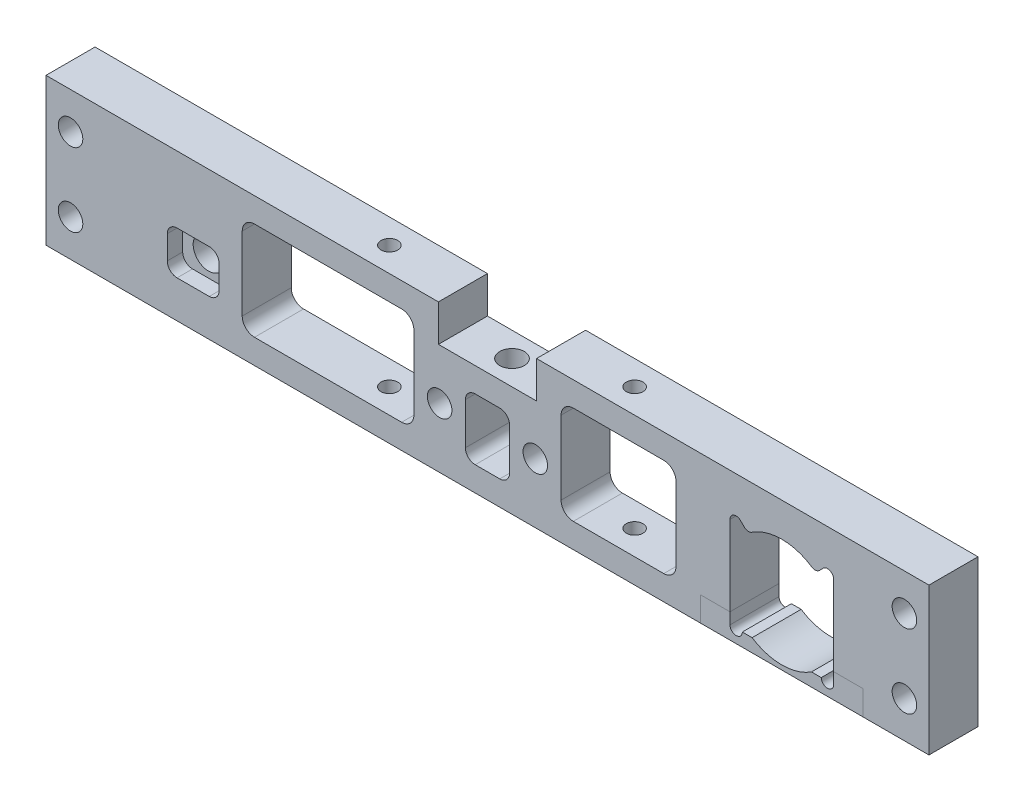
SolidWorks part; units mm, degrees
material "6061-T6 (SS)"
ref_plane "Front Plane" through (0, 0, 0) normal (0, 0, 1) x (1, 0, 0)
ref_plane "Top Plane" through (0, 0, 0) normal (0, 1, 0) x (1, 0, 0)
ref_plane "Right Plane" through (0, 0, 0) normal (1, 0, 0) x (0, 0, -1)
sketch "Sketch1" plane through (0, 0, 0) normal (0, 0, 1) x (1, 0, 0)
  line L1 (-190.5, -19.05) -> (38.1, -19.05)
  line L2 (-190.5, -19.05) -> (-190.5, 19.05)
  line L3 (-190.5, 19.05) -> (38.1, 19.05)
  line L4 (38.1, -19.05) -> (38.1, 19.05)
  line L5 (-190.5, -19.05) -> (38.1, 19.05) construction
  line L6 (-190.5, 19.05) -> (38.1, -19.05) construction
  line L7 (-190.5, 19.05) -> (38.1, 19.05)
  line L8 (-190.5, 19.05) -> (-190.5, -19.05)
  line L11 (-190.5, -19.05) -> (38.1, -19.05)
  line L12 (-190.5, -19.05) -> (-190.5, 19.05)
  line L15 (38.1, -19.05) -> (-190.5, -19.05)
  line L16 (38.1, -19.05) -> (38.1, 19.05)
  line L20 (38.1, -19.05) -> (38.1, 19.05)
  point P0 (0, 0)
  point P14 (-76.2, 0)
  dimension "D1" = 38.1
  dimension "D2" = 228.6
  dimension "D3" = 38.1
extrude "Boss-Extrude1" add sketch "Sketch1" along normal blind 12.7
sketch "Sketch5" plane through (0, 0, 12.7) normal (0, 0, 1) x (1, 0, 0)
  line L0 (0, -3.81) -> (11.8187, 8.0087) construction
  line L1 (0, -3.81) -> (11.8187, -3.81) construction
  line L2 (0, -3.81) -> (0, 8.0087) construction
  line L3 (0, 8.0087) -> (11.8187, 8.0087) construction
  line L4 (11.8187, -3.81) -> (11.8187, 8.0087) construction
  line L5 (-10.6872, 9.1402) -> (-8.7721, 7.2252)
  line L6 (0, -3.81) -> (11.8187, -3.81) construction
  line L7 (0, -3.81) -> (0, -15.6287) construction
  line L8 (0, -15.6287) -> (11.8187, -15.6287) construction
  line L9 (11.8187, -3.81) -> (11.8187, -15.6287) construction
  line L10 (0, -3.81) -> (-11.8187, -3.81) construction
  line L11 (0, -3.81) -> (0, -15.6287) construction
  line L12 (0, -15.6287) -> (-11.8187, -15.6287) construction
  line L13 (-11.8187, -3.81) -> (-11.8187, -15.6287) construction
  line L14 (0, -3.81) -> (-11.8187, -3.81) construction
  line L15 (0, -3.81) -> (0, 8.0087) construction
  line L16 (0, 8.0087) -> (-11.8187, 8.0087) construction
  line L17 (-11.8187, -3.81) -> (-11.8187, 8.0087) construction
  line L18 (-13.4189, 8.0087) -> (-13.4189, -15.6287)
  line L19 (13.4189, 8.0087) -> (13.4189, -15.6287)
  line L20 (10.9269, 9.3374) -> (8.7958, 7.2063)
  line L21 (-13.4189, -15.6287) -> (-13.4189, -19.05)
  line L22 (-190.5, -19.05) -> (38.1, -19.05) construction
  line L23 (-13.4189, -19.05) -> (13.4189, -19.05)
  line L24 (13.4189, -19.05) -> (13.4189, -15.6287)
  line L25 (-10.2185, -15.6287) -> (-7.6839, -15.6287)
  line L26 (10.2185, -15.6287) -> (7.6839, -15.6287)
  circle A0 centre (0, -3.81) radius 14.097 construction
  circle A1 centre (11.8187, 8.0087) radius 1.6002
  circle A2 centre (-11.8187, 8.0087) radius 1.6002
  circle A3 centre (-11.8187, -15.6287) radius 1.6002
  circle A4 centre (11.8187, -15.6287) radius 1.6002
  arc A5 (-8.7721, 7.2252) -> (8.7958, 7.2063) centre (0, -3.81) cw
  arc A6 (-7.6839, -15.6287) -> (7.6839, -15.6287) centre (0, -3.81) ccw
  point P6 (9.9681, 6.1581)
  point P7 (10.6872, 6.8772)
  line M8 (-190.5, -19.05) -> (38.1, -19.05)
  dimension "D1" = 28.194
  dimension "D2" = 3.2004
  dimension "D3" = 1.017
  dimension "D4" = 45
  dimension "D5" = 45
  dimension "D6" = 15.24
extrude "Cut-Extrude4" cut sketch "Sketch5" against normal through all contours A5 L5 A2 L18 A3 L21 L24 A4 L19 A1 L20 M8 | A4 | A3 | A2 | A1 L20
fillet "Fillet1" radius 1.5875 2 edges at (8.7958, 7.2063, 6.35) (-8.7721, 7.2252, 6.35)
sketch "Sketch6" plane through (0, 0, 12.7) normal (0, 0, 1) x (1, 0, 0)
  line L0 (-190.5, 19.05) -> (38.1, 19.05) construction
  line L1 (-88.9, 19.05) -> (-63.5, 19.05)
  line L2 (-88.9, 19.05) -> (-88.9, 9.525)
  line L3 (-88.9, 9.525) -> (-63.5, 9.525)
  line L4 (-63.5, 19.05) -> (-63.5, 9.525)
  point P6 (-76.2, 9.525)
  point P7 (-76.2, 19.05)
  point P8 (-88.9, 19.05)
  dimension "D1" = 9.525
  dimension "D2" = 25.4
  dimension "D3" = 0
extrude "Cut-Extrude5" cut sketch "Sketch6" against normal through all
sketch "Sketch7" plane through (0, 0, 12.7) normal (0, 0, 1) x (1, 0, 0)
  line L0 (-88.9, 9.525) -> (-63.5, 9.525) construction
  line L1 (-81.915, -12.7) -> (-70.485, -12.7)
  line L2 (-81.915, -12.7) -> (-81.915, 3.175)
  line L3 (-81.915, 3.175) -> (-70.485, 3.175)
  line L4 (-70.485, -12.7) -> (-70.485, 3.175)
  line L5 (-190.5, -19.05) -> (38.1, -19.05) construction
  point P4 (-76.2, 9.525)
  point P5 (-76.2, 3.175)
  dimension "D1" = 11.43
  dimension "D2" = 6.35
  dimension "D3" = 6.35
extrude "Cut-Extrude6" cut sketch "Sketch7" against normal through all
sketch "Sketch8" plane through (0, 9.525, 0) normal (0, 1, 0) x (1, 0, 0)
  line L0 (-88.9, 0) -> (-63.5, 0) construction
  line L1 (-88.9, -12.7) -> (-63.5, -12.7) construction
  circle A0 centre (-76.2, -6.35) radius 3.175
  point P2 (-76.2, 0)
  point P3 (-76.2, -12.7)
  dimension "D1" = 6.35
  dimension "D2" = 6.35
extrude "Cut-Extrude7" cut sketch "Sketch8" against normal up to surface (6.35 mm away) up to face at (-76.2, 3.175, 6.35)
sketch "Sketch9" plane through (0, 0, 0) normal (0, 0, -1) x (-1, 0, 0)
  line L0 (-38.1, -19.05) -> (-38.1, 19.05) construction
  line L1 (-31.75, 9.525) -> (184.15, 9.525) construction
  line L2 (-31.75, 9.525) -> (-31.75, -9.525) construction
  line L3 (-31.75, -9.525) -> (184.15, -9.525) construction
  line L4 (184.15, 9.525) -> (184.15, -9.525) construction
  line L5 (190.5, -19.05) -> (190.5, 19.05) construction
  line L6 (190.5, 19.05) -> (88.9, 19.05) construction
  line L7 (190.5, -19.05) -> (-38.1, -19.05) construction
  circle A0 centre (-31.75, 9.525) radius 3.175
  circle A1 centre (-31.75, -9.525) radius 3.175
  circle A2 centre (184.15, 9.525) radius 3.175
  circle A3 centre (184.15, -9.525) radius 3.175
  dimension "D2" = 6.35
  dimension "D3" = 6.35
  dimension "D1" = 6.35
  dimension "D4" = 9.525
  dimension "D5" = 9.525
extrude "Cut-Extrude8" cut sketch "Sketch9" against normal through all
sketch "Sketch10" plane through (0, 0, 0) normal (0, 0, -1) x (-1, 0, 0)
  circle A0 centre (-31.75, 9.525) radius 4.7625
  circle A1 centre (-31.75, -9.525) radius 4.7625
  circle A2 centre (184.15, 9.525) radius 4.7625
  circle A3 centre (184.15, -9.525) radius 4.7625
  dimension "D1" = 9.525
extrude "Cut-Extrude9" cut sketch "Sketch10" against normal blind 6.35
sketch "Sketch11" plane through (0, 0, 0) normal (0, 0, -1) x (-1, 0, 0)
  line L0 (-21.0389, -19.05) -> (-21.0389, -12.7)
  line L1 (190.5, -19.05) -> (-38.1, -19.05) construction
  line L2 (-21.0389, -12.7) -> (21.0389, -12.7)
  line L3 (21.0389, -12.7) -> (21.0389, -19.05)
  line L4 (-13.4189, 8.0087) -> (-13.4189, -15.6287) construction
  line L5 (13.4189, 8.0087) -> (13.4189, -15.6287) construction
  dimension "D1" = 7.62
  dimension "D2" = 7.62
  dimension "D3" = 6.35
surface "Surface-Extrude1" sketch "Sketch11" parameters "D1"=12.7
split "Split1" trimming surface bodies 113 bodies to split 112 resulting bodies 114 115
fillet "Fillet2" radius 2.54 4 edges at (-70.485, -12.7, 6.35) (-81.915, 3.175, 6.35) (-70.485, 3.175, 6.35) (-81.915, -12.7, 6.35)
sketch "Sketch12" plane through (0, -19.05, 0) normal (0, -1, 0) x (1, 0, 0)
  line L0 (-21.0389, 12.7) -> (21.0389, 12.7) construction
  line L1 (-21.0389, 0) -> (-21.0389, 12.7) construction
  line L2 (21.0389, 12.7) -> (21.0389, 0) construction
  circle A0 centre (-17.2289, 6.35) radius 1.4224
  circle A1 centre (17.2289, 6.35) radius 1.4224
  dimension "D3" = 2.8448
  dimension "D4" = 2.8448
  dimension "D1" = 6.35
  dimension "D2" = 6.35
  dimension "D5" = 3.81
  dimension "D6" = 3.81
extrude "Cut-Extrude10" cut sketch "Sketch12" against normal blind 15.24
chamfer "Chamfer1" distance 2.1082 angle 41 1 edges at (18.6513, -19.05, 6.35) first distance on face at (17.2289, -12.7, 7.7724)
chamfer "Chamfer2" distance 2.1082 angle 41 1 edges at (-15.8065, -19.05, 6.35) first distance on face at (-17.2289, -12.7, 7.7724)
sketch "Sketch13" plane through (0, 0, 0) normal (0, 0, -1) x (-1, 0, 0)
  line L0 (63.5, 19.05) -> (-38.1, 19.05) construction
  line L1 (57.15, 12.7) -> (27.3889, 12.7)
  line L2 (57.15, 12.7) -> (57.15, -12.7)
  line L3 (57.15, -12.7) -> (27.3889, -12.7)
  line L4 (27.3889, 12.7) -> (27.3889, -12.7)
  line L5 (190.5, -19.05) -> (21.0389, -19.05) construction
  line L6 (21.0389, -12.7) -> (21.0389, -19.05) construction
  line L7 (63.5, 9.525) -> (63.5, 19.05) construction
  line L8 (88.9, 19.05) -> (88.9, 9.525) construction
  line L9 (95.25, 12.7) -> (139.7, 12.7)
  line L10 (95.25, 12.7) -> (95.25, -12.7)
  line L11 (95.25, -12.7) -> (139.7, -12.7)
  line L12 (139.7, 12.7) -> (139.7, -12.7)
  line L13 (190.5, 19.05) -> (88.9, 19.05) construction
  point P12 (63.5, 14.2875)
  dimension "D1" = 6.35
  dimension "D2" = 6.35
  dimension "D3" = 6.35
  dimension "D4" = 6.35
  dimension "D5" = 6.35
  dimension "D6" = 6.35
  dimension "D7" = 6.35
  dimension "D8" = 44.45
extrude "Cut-Extrude11" cut sketch "Sketch13" against normal through all
fillet "Fillet3" radius 3.175 8 edges at (-57.15, -12.7, 6.35) (-57.15, 12.7, 6.35) (-27.3889, 12.7, 6.35) (-27.3889, -12.7, 6.35) (-95.25, 12.7, 6.35) (-139.7, 12.7, 6.35) (-139.7, -12.7, 6.35) (-95.25, -12.7, 6.35)
sketch "Sketch14" plane through (0, 19.05, 0) normal (0, 1, 0) x (1, 0, 0)
  line L0 (-190.5, 0) -> (-88.9, 0) construction
  line L1 (-63.5, 0) -> (38.1, 0) construction
  line L2 (-63.5, 0) -> (-63.5, -12.7) construction
  line L3 (-88.9, 0) -> (-88.9, -12.7) construction
  circle A0 centre (-107.95, -6.35) radius 2.159
  circle A1 centre (-44.45, -6.35) radius 2.159
  dimension "D1" = 4.318
  dimension "D2" = 4.318
  dimension "D3" = 6.35
  dimension "D4" = 6.35
  dimension "D5" = 19.05
  dimension "D6" = 19.05
extrude "Cut-Extrude12" cut sketch "Sketch14" against normal through all
sketch "Sketch15" plane through (0, 0, 0) normal (0, 0, -1) x (-1, 0, 0)
  line L0 (0, -3.81) -> (-38.1, -3.81) construction
  line L1 (-38.1, -19.05) -> (-38.1, 19.05) construction
  line L2 (152.4, -3.81) -> (190.5, -3.81) construction
  line L3 (190.5, -19.05) -> (190.5, 19.05) construction
  circle A0 centre (0, -3.81) radius 14.097 construction
  arc A1 (7.7341, 7.9759) -> (-7.7572, 7.9608) centre (0, -3.81) ccw construction
  circle A2 centre (152.4, -3.81) radius 3.175
  dimension "D1" = 6.35
extrude "Cut-Extrude13" cut sketch "Sketch15" against normal through all
sketch "Sketch16" plane through (0, 0, 12.7) normal (0, 0, 1) x (1, 0, 0)
  line L1 (-149.1738, 1.778) -> (-155.6262, 1.778) construction
  line L2 (-155.6262, 1.778) -> (-158.8525, -3.81) construction
  line L3 (-158.8525, -3.81) -> (-155.6262, -9.398) construction
  line L4 (-155.6262, -9.398) -> (-149.1738, -9.398) construction
  line L5 (-149.1738, -9.398) -> (-145.9475, -3.81) construction
  line L6 (-145.9475, -3.81) -> (-149.1738, 1.778) construction
  line L7 (-159.1065, -9.398) -> (-145.6935, -9.398)
  line L8 (-159.1065, -9.398) -> (-159.1065, 1.778)
  line L9 (-159.1065, 1.778) -> (-145.6935, 1.778)
  line L10 (-145.6935, -9.398) -> (-145.6935, 1.778)
  line L11 (-159.1065, -9.398) -> (-145.6935, 1.778) construction
  line L12 (-159.1065, 1.778) -> (-145.6935, -9.398) construction
  circle A0 centre (-152.4, -3.81) radius 5.588 construction
  dimension "D1" = 11.176
  dimension "D2" = 0.254
extrude "Cut-Extrude14" cut sketch "Sketch16" against normal blind 4
fillet "Fillet4" radius 2.54 4 edges at (-159.1065, -9.398, 10.7) (-159.1065, 1.778, 10.7) (-145.6935, 1.778, 10.7) (-145.6935, -9.398, 10.7)
sketch "Sketch17" plane through (0, 0, 0) normal (0, 0, -1) x (-1, 0, 0)
  line L0 (190.5, -19.05) -> (21.0389, -19.05) construction
  line L1 (63.8175, -3.556) -> (57.15, -3.556) construction
  line L2 (57.15, -9.525) -> (57.15, 9.525) construction
  line L3 (63.8175, -3.556) -> (70.485, -3.556) construction
  line L4 (70.485, -10.16) -> (70.485, 0.635) construction
  line L5 (81.915, -3.556) -> (88.5825, -3.556) construction
  line L7 (88.5825, -3.556) -> (95.25, -3.556) construction
  line L8 (95.25, 9.525) -> (95.25, -9.525) construction
  line L9 (81.915, 0.635) -> (81.915, -10.16) construction
  circle A0 centre (63.8175, -3.556) radius 3.175
  circle A1 centre (88.5825, -3.556) radius 3.175
  dimension "D1" = 6.35
  dimension "D2" = 15.494
extrude "Cut-Extrude15" cut sketch "Sketch17" against normal through all
sketch "Sketch18" plane through (0, 0, 0) normal (0, 0, -1) x (-1, 0, 0)
  circle A0 centre (152.4, -3.81) radius 4
  dimension "D1" = 8
extrude "Cut-Extrude16" cut sketch "Sketch18" against normal through all
